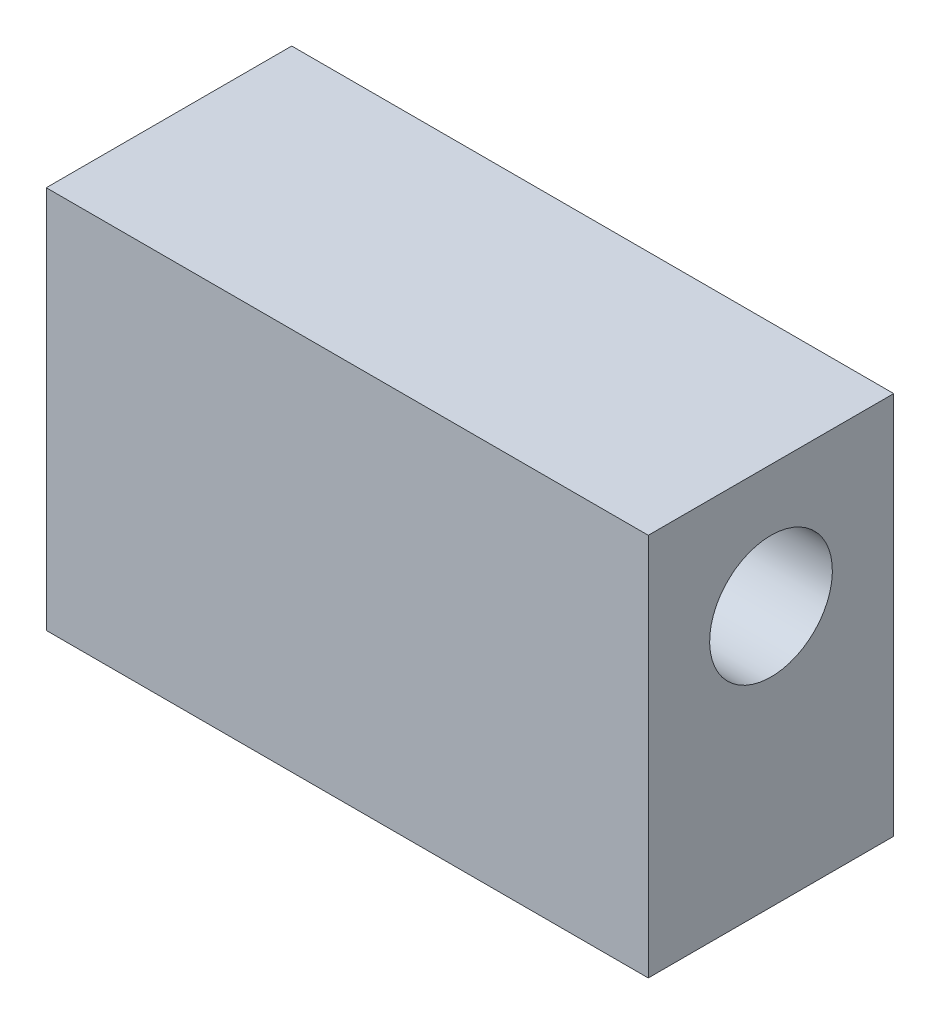
SolidWorks part; units mm, degrees
material "1060 Alloy"
ref_plane "Front" through (0, 0, 0) normal (0, 0, 1) x (1, 0, 0)
ref_plane "Top" through (0, 0, 0) normal (0, 1, 0) x (1, 0, 0)
ref_plane "Right" through (0, 0, 0) normal (1, 0, 0) x (0, 0, -1)
sketch "Sketch3" plane through (0, 0, 0) normal (0, 0, 1) x (1, 0, 0)
  line L0 (-0.127, -6.35) -> (30.1755, -6.35)
  line L1 (0, 0) -> (31.1484, 0)
  line L2 (0, 0) -> (0, -19.8376)
  line L3 (0, -19.8376) -> (31.1484, -19.8376)
  line L4 (31.1484, 0) -> (31.1484, -19.8376)
  line L5 (15.5742, -19.8376) -> (15.5742, 0) construction
  line L6 (15.5742, -6.35) -> (8.0621, -19.3614) construction
  line L15 (12.5496, -11.5887) -> (15.5742, -13.335) construction
  line L16 (15.5742, -6.35) -> (22.9274, -19.0862) construction
  circle A0 centre (15.5742, -6.35) radius 6.0492 construction
  point P14 (0, -6.35)
  point P17 (9.525, -6.35)
  point P19 (31.1484, -6.35)
  point P20 (7.7871, -19.8376)
  point P24 (23.3613, -19.8376)
  dimension "D2" = 6.35
  dimension "D6" = 3.4925
  dimension "D3" = 60
  dimension "D1" = 9.525
  dimension "D4" = 9.525
  dimension "D5" = 60
extrude "Boss-Extrude1" add sketch "Sketch3" along normal mid plane 12.7
sketch "Sketch4" plane through (0, 0, 0) normal (-1, 0, 0) x (0, 0, 1)
  circle A0 centre (0, -6.35) radius 3.175
  dimension "D1" = 6.35
extrude "Cut-Extrude1" cut sketch "Sketch4" against normal blind 9.525
ref_plane "Plane1" through (7.7871, -19.8376, 0) normal (-0.5, -0.866, 0) x (-0.866, 0.5, 0)
ref_plane "Mirror Plane" through (15.5742, 0, 0) normal (-1, 0, 0) x (0, 0, 1)
sketch "Sketch5" plane through (7.7871, -19.8376, 0) normal (-0.5, -0.866, 0) x (-0.866, 0.5, 0)
  circle A0 centre (0, 0) radius 3.175
  dimension "D1" = 6.35
extrude "Cut-Extrude5" cut sketch "Sketch5" against normal blind 9.525 and the other way up to next
sketch "Sketch6" plane through (0, 0, -6.35) normal (0, 0, -1) x (-1, 0, 0)
  circle A0 centre (-15.5742, -6.35) radius 3.175
  dimension "D1" = 6.35
extrude "Cut-Extrude6" cut sketch "Sketch6" against normal blind 9.525
mirror "Mirror1" about plane through (15.5742, 0, 0) normal (-1, 0, 0) of "Cut-Extrude5", "Cut-Extrude1"
equation "\"truss_member_od\" = .25in"
equation "\"truss_member_id\" = 0in"
equation "\"truss_member_L1\" = 2.75in"
equation "\"connector_hole_depth\" = .375in"
equation "\"D1@Boss-Extrude1\"=\"truss_member_od\"*2"
equation "\"D6@Sketch3\"=\"truss_member_od\"/2*1.1"
equation "\"D1@Sketch4\"=\"truss_member_od\""
equation "\"D1@Cut-Extrude1\"=\"connector_hole_depth\""
equation "\"D1@Sketch3\"=\"connector_hole_depth\""
equation "\"D4@Sketch3\"=\"connector_hole_depth\""
equation "\"D1@Sketch5\"=\"truss_member_od\""
equation "\"D1@Cut-Extrude5\"=\"connector_hole_depth\""
equation "\"D1@Cut-Extrude6\"=\"connector_hole_depth\""
equation "\"D1@Sketch6\"=\"truss_member_od\""
